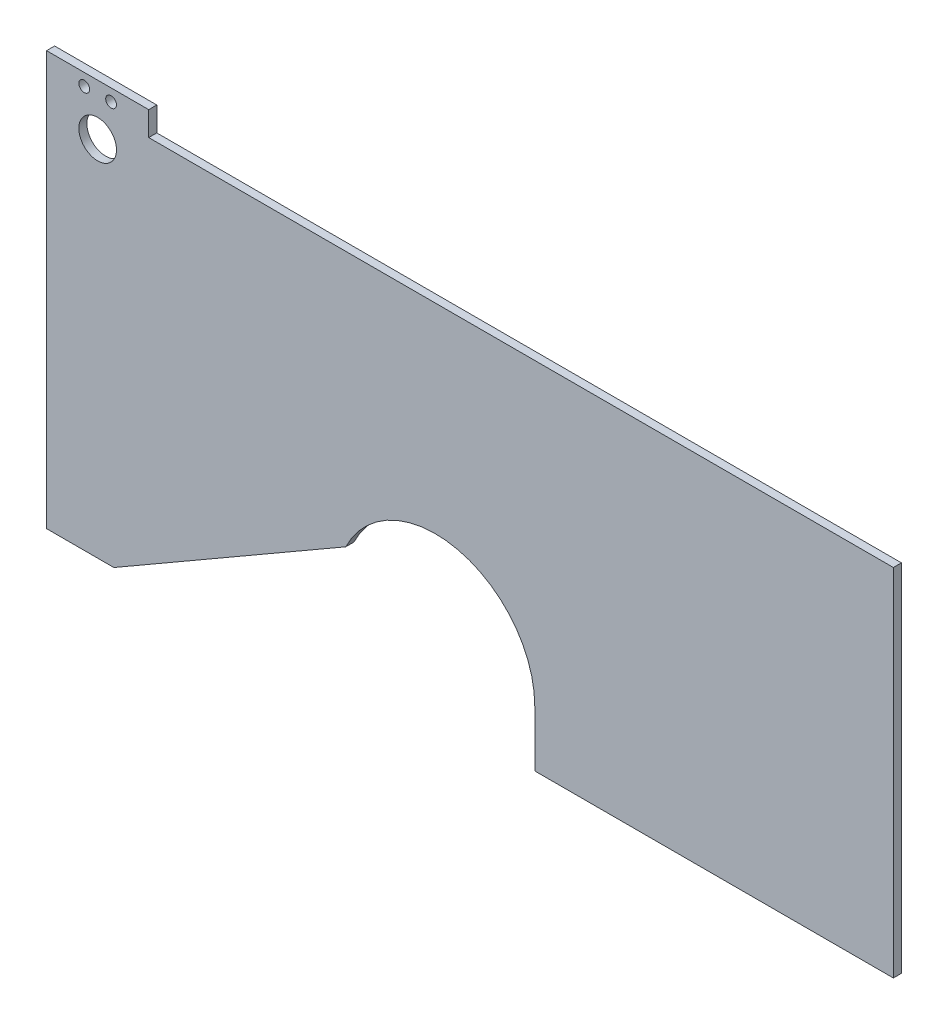
SolidWorks part; units mm, degrees
ref_plane "Front Plane" through (0, 0, 0) normal (0, 0, 1) x (1, 0, 0)
ref_plane "Top Plane" through (0, 0, 0) normal (0, 1, 0) x (1, 0, 0)
ref_plane "Right Plane" through (0, 0, 0) normal (1, 0, 0) x (0, 0, -1)
sketch "Sketch2" plane through (0, 0, 0) normal (0, 0, 1) x (1, 0, 0)
  line L0 (25.0304, 0) -> (111.2865, 49.8)
  line L1 (0, 0) -> (25.0304, 0)
  line L2 (0, 0) -> (0, 154)
  line L4 (315, 0) -> (315, 145)
  line L5 (181.6, 33.7) -> (181.6, 0)
  line L6 (181.6, 0) -> (315, 0)
  line L7 (19, 135) -> (19, 164.3674) construction
  line L11 (38, 145) -> (315, 145)
  line L12 (0, 154) -> (19, 154)
  line L13 (19, 154) -> (38, 154)
  line L14 (38, 154) -> (38, 145)
  line L15 (19, 135) -> (50019, 135) construction
  line L20 (19, 135) -> (19, -49865) construction
  circle A0 centre (19, 135) radius 7
  arc A1 (181.6, 33.7) -> (111.2865, 49.8) centre (144.6, 33.7) ccw
  circle A2 centre (14, 149.5) radius 2
  circle A3 centre (24, 149.5) radius 2
  point P19 (19, 154)
  dimension "D3" = 135
  dimension "D4" = 19
  dimension "D5" = 14
  dimension "D6" = 74
  dimension "D7" = 170.4
  dimension "D8" = 33.7
  dimension "D13" = 4
  dimension "D14" = 5
  dimension "D15" = 14.5
  dimension "D1" = 315
  dimension "D2" = 154
  dimension "D9" = 30
  dimension "D10" = 99.6
  dimension "D11" = 19
extrude "Boss-Extrude2" add sketch "Sketch2" along normal blind 3
sketch "Sketch3" plane through (0, 0, 3) normal (0, 0, 1) x (1, 0, 0)
  line L0 (315, 0) -> (315, 145) construction
  line L1 (181.6, 0) -> (315, 0)
  line L2 (181.6, 0) -> (181.6, 12.75)
  line L3 (181.6, 12.75) -> (315, 12.75)
  line L4 (315, 0) -> (315, 12.75)
  dimension "D1" = 12.75
extrude "Cut-Extrude1" cut sketch "Sketch3" against normal through all
sketch "Sketch4" plane through (0, 0, 3) normal (0, 0, 1) x (1, 0, 0)
  line L0 (19, 135) -> (19, -49865) construction
  line L1 (19, 135) -> (-49981, 135) construction
